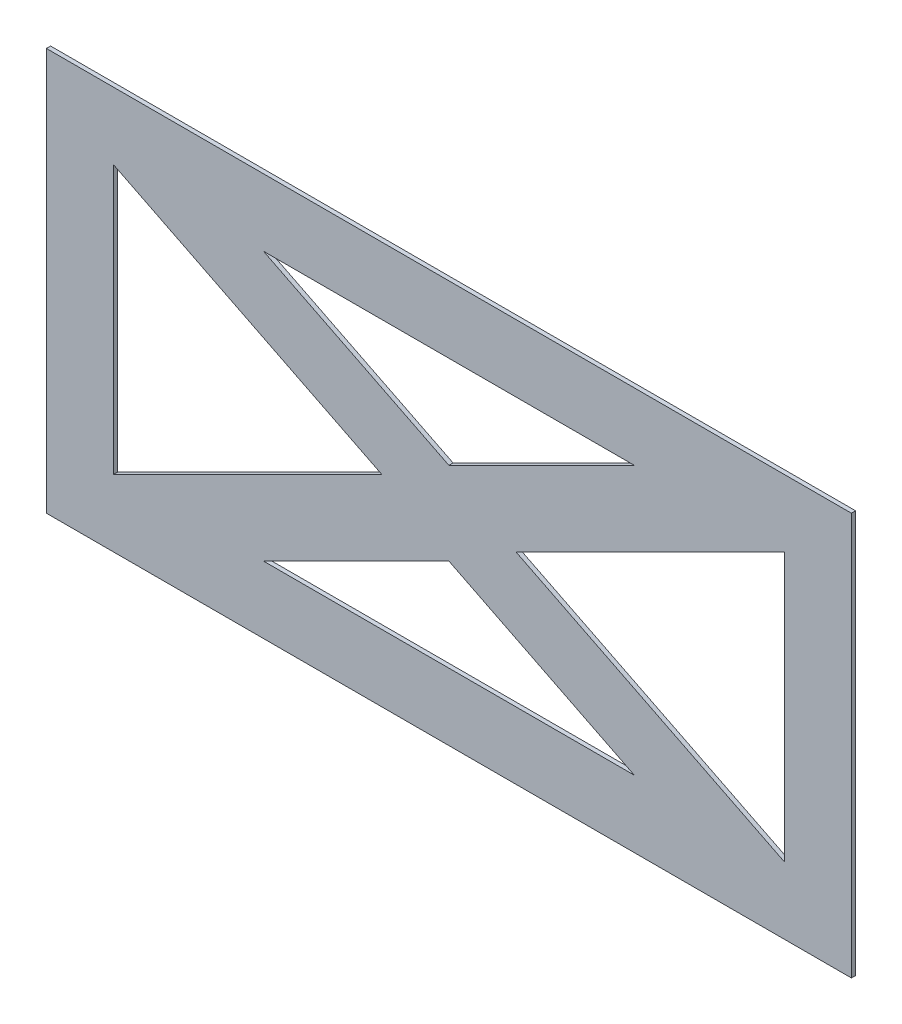
SolidWorks part; units mm, degrees
ref_plane "Front Plane" through (0, 0, 0) normal (0, 0, 1) x (1, 0, 0)
ref_plane "Top Plane" through (0, 0, 0) normal (0, 1, 0) x (1, 0, 0)
ref_plane "Right Plane" through (0, 0, 0) normal (1, 0, 0) x (0, 0, -1)
sketch "Sketch1" plane through (0, 0, 0) normal (0, 0, 1) x (1, 0, 0)
  line L0 (-127, 50.8) -> (-127, -50.8)
  line L1 (-152.4, -76.2) -> (152.4, -76.2)
  line L2 (-152.4, -76.2) -> (-152.4, 76.2)
  line L3 (-152.4, 76.2) -> (152.4, 76.2)
  line L4 (152.4, -76.2) -> (152.4, 76.2)
  line L5 (-152.4, -76.2) -> (152.4, 76.2) construction
  line L6 (-152.4, 76.2) -> (152.4, -76.2) construction
  line L7 (-127, -50.8) -> (-25.4, 0)
  line L8 (-25.4, 0) -> (-127, 50.8)
  line L9 (-70.2039, 50.8) -> (70.2039, 50.8)
  line L10 (70.2039, 50.8) -> (0, 15.6981)
  line L11 (0, 15.6981) -> (-70.2039, 50.8)
  line L12 (0, -15.6981) -> (-70.2039, -50.8)
  line L13 (-70.2039, -50.8) -> (70.2039, -50.8)
  line L14 (70.2039, -50.8) -> (0, -15.6981)
  line L15 (25.4, 0) -> (127, 50.8)
  line L16 (127, 50.8) -> (127, -50.8)
  line L17 (127, -50.8) -> (25.4, 0)
  point P0 (0, 0)
  point P17 (-3.4746, 20.1559)
  point P19 (0, 0)
  point P20 (0, 0)
  point P21 (33.0519, 0)
  point P22 (127, -45.7701)
  point P23 (86.06, -50.8)
  point P24 (67.7967, 50.8)
  point P25 (-127, 46.974)
  point P26 (-127, -46.974)
  point P27 (-127, 50.8)
  point P28 (0, 9.9106)
  point P29 (87.3963, -50.8)
  point P30 (0, 7.6834)
  dimension "D1" = 304.8
  dimension "D2" = 152.4
  dimension "D3" = 25.4
  dimension "D4" = 25.4
  dimension "D5" = 25.4
  dimension "D6" = 25.4
  dimension "D7" = 25.4
  dimension "D8" = 25.4
extrude "Boss-Extrude1" add sketch "Sketch1" along normal mid plane 1.5875
